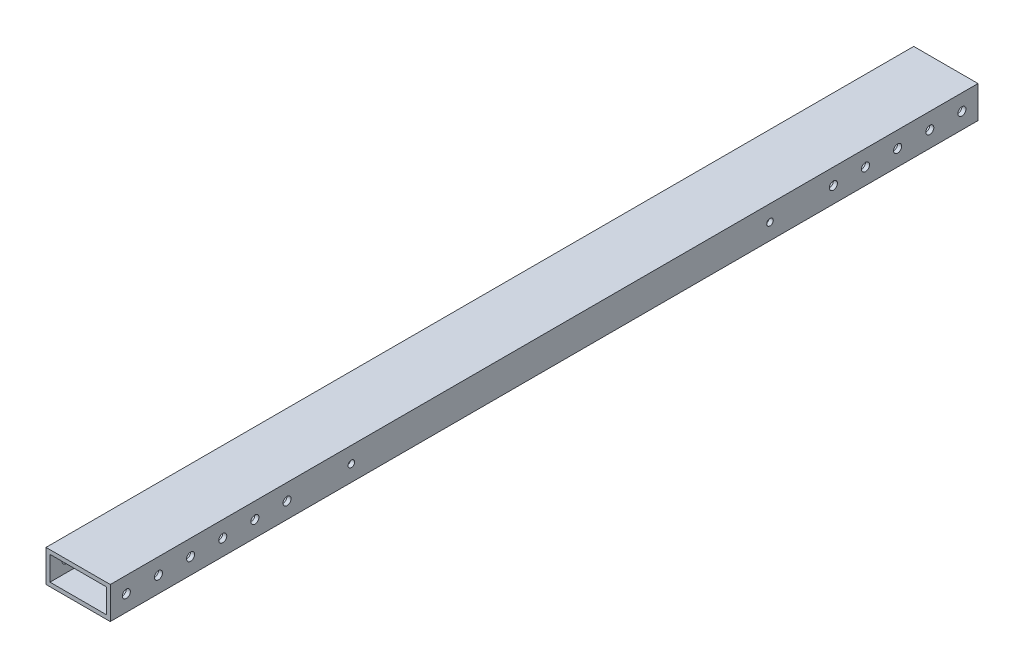
SolidWorks part; units mm, degrees
material "6061 Alloy"
ref_plane "Front Plane" through (0, 0, 0) normal (0, 0, 1) x (1, 0, 0)
ref_plane "Top Plane" through (0, 0, 0) normal (0, 1, 0) x (1, 0, 0)
ref_plane "Right Plane" through (0, 0, 0) normal (1, 0, 0) x (0, 0, -1)
sketch "Sketch1" plane through (0, 0, 0) normal (0, 0, 1) x (1, 0, 0)
  line L0 (-22.225, 9.525) -> (22.225, 9.525)
  line L2 (-25.4, 12.7) -> (25.4, 12.7)
  line L3 (-25.4, 12.7) -> (-25.4, -12.7)
  line L4 (-25.4, -12.7) -> (25.4, -12.7)
  line L5 (25.4, 12.7) -> (25.4, -12.7)
  line L10 (22.225, 9.525) -> (22.225, -9.525)
  line L11 (-22.225, -9.525) -> (22.225, -9.525)
  line L12 (-22.225, 9.525) -> (-22.225, -9.525)
  point P12 (0, 12.7)
  point P14 (25.4, 0)
  dimension "Wall Thickness" = 3.175
  dimension "Outside Width" = 50.8
  dimension "Outside Height" = 25.4
  dimension "Inside Height" = 19.05
  dimension "Inside Width" = 44.45
sketch "Sketch2" plane through (0, 0, 0) normal (1, 0, 0) x (0, 0, -1)
  line L0 (342.9, 0) -> (-342.9, 0)
  point P4 (0, 0)
  point P7 (-342.9, 0)
  point P10 (342.9, 0)
  dimension "Length" = 685.8
sketch "Sketch3" plane through (0, 0, 0) normal (0, 0, 1) x (1, 0, 0)
  line L21 (25.4, 12.7) -> (-25.4, 12.7)
  line L22 (25.4, -12.7) -> (25.4, 12.7)
  line L23 (-25.4, -12.7) -> (25.4, -12.7)
  line L24 (-25.4, 12.7) -> (-25.4, -12.7)
  line L25 (25.4, 12.7) -> (-25.4, 12.7)
  line L26 (25.4, -12.7) -> (25.4, 12.7)
  line L27 (-25.4, -12.7) -> (25.4, -12.7)
  line L28 (-25.4, 12.7) -> (-25.4, -12.7)
  line L29 (22.225, 9.525) -> (-22.225, 9.525)
  line L30 (22.225, -9.525) -> (22.225, 9.525)
  line L31 (-22.225, -9.525) -> (22.225, -9.525)
  line L32 (-22.225, 9.525) -> (-22.225, -9.525)
  line L33 (22.225, 9.525) -> (-22.225, 9.525)
  line L34 (22.225, -9.525) -> (22.225, 9.525)
  line L35 (-22.225, -9.525) -> (22.225, -9.525)
  line L36 (-22.225, 9.525) -> (-22.225, -9.525)
  dimension "D1" = 0
  dimension "D2" = 0
extrude "Boss-Extrude1" add sketch "Sketch3" along normal up to vertex (342.9 mm away) and the other way up to vertex (342.9 mm away) up to point (0, 0, 342.9) other way up to point (0, 0, -342.9)
sketch "Drawing Reference" plane through (0, 0, 0) normal (1, 0, 0) x (0, 0, -1)
  line L0 (-342.9, 0) -> (342.9, 0) construction
  line L1 (0, -12.7) -> (0, 12.7) construction
  line L2 (-342.9, -12.7) -> (342.9, -12.7) construction
  line L5 (-342.9, 12.7) -> (342.9, 12.7) construction
  point P7 (-306.324, 0)
  point P8 (306.324, 0)
  dimension "D1" = 36.576
sketch "Sketch5" plane through (25.4, 0, 0) normal (1, 0, 0) x (0, 0, -1)
  line L0 (-342.9, 0) -> (-279.4, 0)
  line L1 (-342.9, -12.7) -> (-342.9, 12.7) construction
  line L2 (-279.4, 0) -> (-254, 0)
  line L3 (-254, 0) -> (-228.6, 0)
  line L4 (-228.6, 0) -> (-203.2, 0)
sketch "Sketch8" plane through (25.4, 0, 0) normal (1, 0, 0) x (0, 0, -1)
  line L0 (342.9, 0) -> (304.8, 0)
  line L1 (342.9, -12.7) -> (342.9, 12.7) construction
  line L2 (304.8, 0) -> (279.4, 0)
  line L3 (279.4, 0) -> (254, 0)
  line L4 (254, 0) -> (228.6, 0)
  line L5 (342.9, 0) -> (330.2, 0)
  point P5 (0, 0)
  point P10 (0, 0)
  point P11 (0, 0)
hole_wizard "1/4 (0.25) Diameter Hole3" positions "Sketch12" profile "Sketch13" hole size "1/4" standard "ANSI Inch" end condition through all
sketch "Sketch12" plane through (-25.4, 0, 0) normal (-1, 0, 0) x (0, 0, 1)
  point P4 (-330.2, 0)
sketch "Sketch13" plane through (-25.4, 0, -330.2) normal (0, 1, 0) x (0, 0, 1)
  line L0 (0, 0) -> (0, 50.8)
  line L1 (0, 50.8) -> (3.175, 50.8)
  line L2 (3.175, 50.8) -> (3.175, 0)
  line L5 (3.175, 0) -> (0, 0)
  line L11 (0, -6.35) -> (0, 107.95) construction
  dimension "Thru Hole Dia." = 6.35
  dimension "Thru Hole Depth" = 50.8
hole_wizard "1/4 (0.25) Diameter Hole4" positions "Sketch14" profile "Sketch15" hole size "1/4" standard "ANSI Inch" end condition through all
sketch "Sketch14" plane through (-25.4, 0, 0) normal (-1, 0, 0) x (0, 0, 1)
  point P0 (304.8, 0)
  point P3 (330.2, 0)
sketch "Sketch15" plane through (-25.4, 0, 304.8) normal (0, 1, 0) x (0, 0, 1)
  line L0 (0, 0) -> (0, 50.8)
  line L1 (0, 50.8) -> (3.175, 50.8)
  line L2 (3.175, 50.8) -> (3.175, 0)
  line L5 (3.175, 0) -> (0, 0)
  line L11 (0, -6.35) -> (0, 107.95) construction
  dimension "Thru Hole Dia." = 6.35
  dimension "Thru Hole Depth" = 50.8
hole_wizard "1/4 (0.25) Diameter Hole5" positions "Sketch17" profile "Sketch18" hole size "1/4" standard "ANSI Inch" end condition through all
sketch "Sketch17" plane through (25.4, 0, 0) normal (1, 0, 0) x (0, 0, -1)
  point P0 (304.8, 0)
  point P3 (279.4, 0)
sketch "Sketch18" plane through (25.4, 0, -304.8) normal (0, 1, 0) x (0, 0, -1)
  line L0 (0, 0) -> (0, 50.8)
  line L1 (0, 50.8) -> (3.175, 50.8)
  line L2 (3.175, 50.8) -> (3.175, 0)
  line L5 (3.175, 0) -> (0, 0)
  line L11 (0, -6.35) -> (0, 107.95) construction
  dimension "Thru Hole Dia." = 6.35
  dimension "Thru Hole Depth" = 50.8
hole_wizard "1/4 (0.25) Diameter Hole6" positions "Sketch19" profile "Sketch20" hole size "1/4" standard "ANSI Inch" end condition through all
sketch "Sketch19" plane through (25.4, 0, 0) normal (1, 0, 0) x (0, 0, -1)
  point P0 (228.6, 0)
  point P3 (254, 0)
sketch "Sketch20" plane through (25.4, 0, -228.6) normal (0, 1, 0) x (0, 0, -1)
  line L0 (0, 0) -> (0, 50.8)
  line L1 (0, 50.8) -> (3.175, 50.8)
  line L2 (3.175, 50.8) -> (3.175, 0)
  line L5 (3.175, 0) -> (0, 0)
  line L11 (0, -6.35) -> (0, 107.95) construction
  dimension "Thru Hole Dia." = 6.35
  dimension "Thru Hole Depth" = 50.8
hole_wizard "1/4 (0.25) Diameter Hole7" positions "Sketch21" profile "Sketch22" hole size "1/4" standard "ANSI Inch" end condition through all
sketch "Sketch21" plane through (25.4, 0, 0) normal (1, 0, 0) x (0, 0, -1)
  point P0 (-203.2, 0)
  point P3 (-228.6, 0)
sketch "Sketch22" plane through (25.4, 0, 203.2) normal (0, 1, 0) x (0, 0, -1)
  line L0 (0, 0) -> (0, 50.8)
  line L1 (0, 50.8) -> (3.175, 50.8)
  line L2 (3.175, 50.8) -> (3.175, 0)
  line L5 (3.175, 0) -> (0, 0)
  line L11 (0, -6.35) -> (0, 107.95) construction
  dimension "Thru Hole Dia." = 6.35
  dimension "Thru Hole Depth" = 50.8
hole_wizard "1/4 (0.25) Diameter Hole8" positions "Sketch23" profile "Sketch24" hole size "1/4" standard "ANSI Inch" end condition through all
sketch "Sketch23" plane through (25.4, 0, 0) normal (1, 0, 0) x (0, 0, -1)
  point P0 (-279.4, 0)
  point P3 (-254, 0)
sketch "Sketch24" plane through (25.4, 0, 279.4) normal (0, 1, 0) x (0, 0, -1)
  line L0 (0, 0) -> (0, 50.8)
  line L1 (0, 50.8) -> (3.175, 50.8)
  line L2 (3.175, 50.8) -> (3.175, 0)
  line L5 (3.175, 0) -> (0, 0)
  line L11 (0, -6.35) -> (0, 107.95) construction
  dimension "Thru Hole Dia." = 6.35
  dimension "Thru Hole Depth" = 50.8
sketch "Sketch25" plane through (25.4, 0, 0) normal (1, 0, 0) x (0, 0, -1)
  line L0 (-203.2, 0) -> (-152.4, 0)
  line L1 (228.6, 0) -> (178.5118, 0)
hole_wizard "13/64 (0.20313) Diameter Hole1" positions "Sketch26" profile "Sketch27" hole size "13/64" standard "ANSI Inch" end condition through all
sketch "Sketch26" plane through (25.4, 0, 0) normal (1, 0, 0) x (0, 0, -1)
  point P0 (-152.4, 0)
  point P3 (178.5118, 0)
sketch "Sketch27" plane through (25.4, 0, 152.4) normal (0, 1, 0) x (0, 0, -1)
  line L0 (0, 0) -> (0, 50.8)
  line L1 (0, 50.8) -> (2.5798, 50.8)
  line L2 (2.5798, 50.8) -> (2.5798, 0)
  line L5 (2.5798, 0) -> (0, 0)
  line L11 (0, -6.35) -> (0, 107.95) construction
  dimension "Thru Hole Dia." = 5.1595
  dimension "Thru Hole Depth" = 50.8
sketch "Sketch30" plane through (-25.4, 0, 0) normal (-1, 0, 0) x (0, 0, 1)
  line L0 (203.2, 0) -> (184.15, 0)
  line L1 (203.2, 0) -> (152.4, 0) construction
  point P0 (-210.2618, 0)
hole_wizard "1/2 (0.5) Diameter Hole1" positions "Sketch33" profile "Sketch34" hole size "1/2" standard "ANSI Inch"
sketch "Sketch33" plane through (-25.4, 0, 0) normal (-1, 0, 0) x (0, 0, 1)
  point P0 (-210.2618, 0)
  point P3 (184.15, 0)
sketch "Sketch34" plane through (-25.4, 0, -210.2618) normal (0, 1, 0) x (0, 0, 1)
  line L0 (0, 0) -> (0, 10.1655)
  line L1 (0, 10.1655) -> (6.35, 6.35)
  line L2 (6.35, 6.35) -> (6.35, 0)
  line L5 (6.35, 0) -> (0, 0)
  line L10 (0, 10.1655) -> (-6.35, 6.35) construction
  line L11 (0, -6.35) -> (0, 107.95) construction
  dimension "Hole Dia." = 12.7
  dimension "Hole Depth" = 6.35
  dimension "Drill Angle" = 118
equation "\"D1@Drawing Reference\"=\"Outside Width@Sketch1\" * 0.72"
